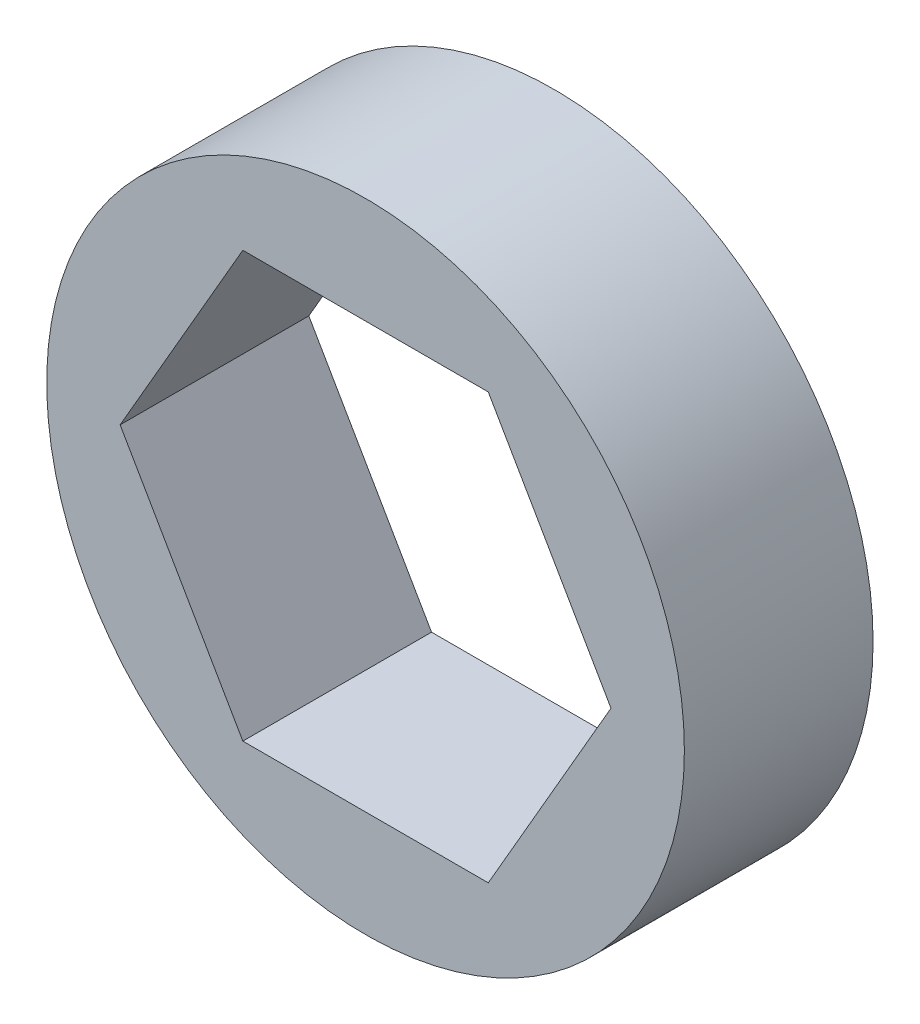
SolidWorks part; units mm, degrees
material "Nylon 101"
ref_plane "Front Plane" through (0, 0, 0) normal (0, 0, 1) x (1, 0, 0)
ref_plane "Top Plane" through (0, 0, 0) normal (0, 1, 0) x (1, 0, 0)
ref_plane "Right Plane" through (0, 0, 0) normal (1, 0, 0) x (0, 0, -1)
sketch "Sketch1" plane through (0, 0, 0) normal (0, 0, 1) x (1, 0, 0)
  line L1 (3.6662, 6.35) -> (-3.6662, 6.35)
  line L2 (-3.6662, 6.35) -> (-7.3323, 0)
  line L3 (-7.3323, 0) -> (-3.6662, -6.35)
  line L4 (-3.6662, -6.35) -> (3.6662, -6.35)
  line L5 (3.6662, -6.35) -> (7.3323, 0)
  line L6 (7.3323, 0) -> (3.6662, 6.35)
  circle A1 centre (0, 0) radius 9.525
  circle A2 centre (0, 0) radius 6.35 construction
  dimension "D1" = 19.05
  dimension ".5" = 12.7
extrude "Boss-Extrude1" add sketch "Sketch1" along normal blind 5.6375
sketch "Sketch2" plane through (0, 0, 0) normal (0, 0, -1) x (-1, 0, 0)
  line L0 (-3.6079, 6.985) -> (3.4241, 6.985) construction
  line L1 (-3.6662, 6.35) -> (3.6662, 6.35) construction
  text T0 "0048" font "Century Gothic" height in points 6
  dimension "D1" = 0.635
extrude "Cut-Extrude1" cut sketch "Sketch2" against normal blind 0.4
